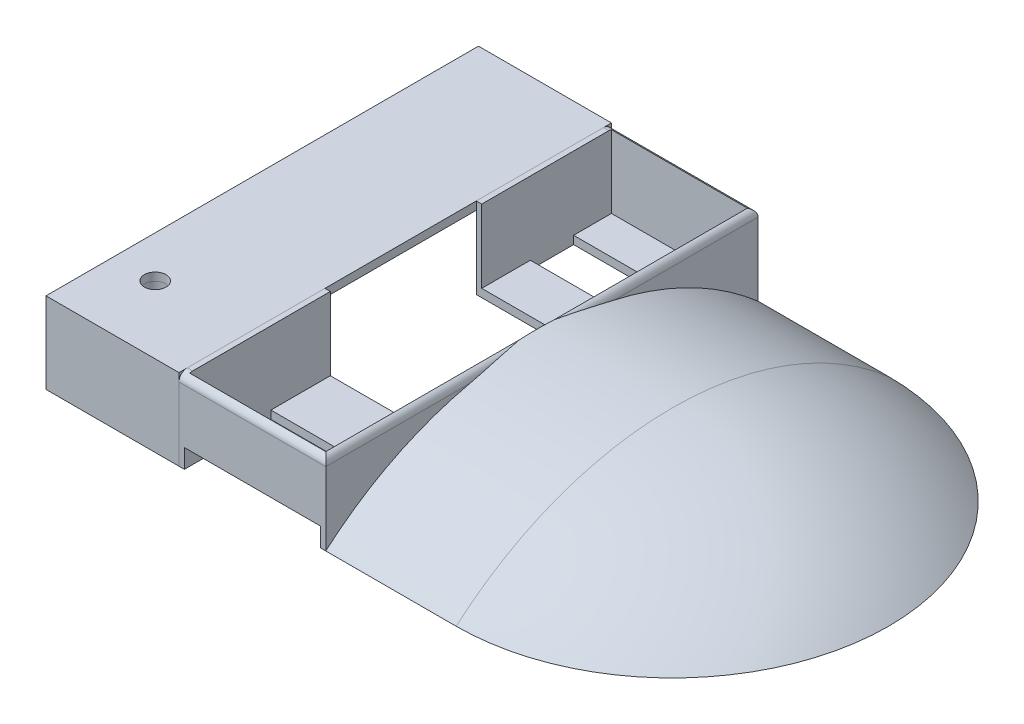
SolidWorks part; units mm, degrees
note: The reader was unsure of these and kept them because the rebuilt part matched: shared geometry of "Sketch11<3>", "Sketch47<2>".
ref_plane "Front Plane" through (0, 0, 0) normal (0, 0, 1) x (1, 0, 0)
ref_plane "Top Plane" through (0, 0, 0) normal (0, 1, 0) x (1, 0, 0)
ref_plane "Right Plane" through (0, 0, 0) normal (1, 0, 0) x (0, 0, -1)
sketch3d "3DSketch2"
  line L1 (0.225, 29.25, -28.4) -> (24.375, 23.2287, -28.4) construction
  dimension "D1" = 0
sketch3d "3DSketch4" plane through (0, 0, 0) normal (0, 0, 1) x (1, 0, 0)
  dimension "D1" = 50
sketch "Sketch1" plane through (0, 0, 0) normal (0, 1, 0) x (1, 0, 0)
  line L1 (-25.875, -40) -> (25.875, -40)
  line L2 (-25.875, -40) -> (-25.875, 40)
  line L3 (-25.875, 40) -> (25.875, 40)
  line L4 (25.875, -40) -> (25.875, 40)
  line L5 (-25.875, -40) -> (25.875, 40) construction
  line L6 (-25.875, 40) -> (25.875, -40) construction
  point P0 (0, 0)
  dimension "D1" = 80
  dimension "D2" = 51.75
extrude "Boss-Extrude1" add sketch "Sketch1" along normal blind 15
shell "Shell3" thickness 1.5
sketch "Sketch4" plane through (-25.875, 0, 0) normal (-1, 0, 0) x (0, 0, 1)
  line L0 (-34.38, 1.6) -> (-28.48, 1.6) construction
  line L1 (-34.38, 3.4) -> (-28.48, 3.4)
  line L2 (-34.38, -0.2) -> (-28.48, -0.2)
  line L3 (-40, 15) -> (-40, 0) construction
  arc A0 (-34.38, 3.4) -> (-34.38, -0.2) centre (-34.38, 1.6) ccw
  arc A1 (-28.48, -0.2) -> (-28.48, 3.4) centre (-28.48, 1.6) ccw
  point P2 (-31.43, 1.6)
  dimension "D1" = 8.57
  dimension "D2" = 5.9
  dimension "D3" = 3.6
extrude "Cut-Extrude2" cut sketch "Sketch4" against normal blind 1.5
sketch "Sketch6" plane through (-25.875, 0, 0) normal (-1, 0, 0) x (0, 0, 1)
  line L0 (-27.6554, 0) -> (40, 0) construction
  line L1 (-24.4, 7.3) -> (-10.75, 7.3)
  line L2 (-24.4, 7.3) -> (-24.4, 0)
  line L3 (-24.4, 0) -> (-10.75, 0)
  line L4 (-10.75, 7.3) -> (-10.75, 0)
  line L5 (-24.4, 7.3) -> (-10.75, 0) construction
  line L6 (-24.4, 0) -> (-10.75, 7.3) construction
  line L8 (-40, 15) -> (-40, 0) construction
  point P6 (-17.575, 3.65)
  dimension "D1" = 7.3
  dimension "D2" = 13.65
  dimension "D3" = 0
  dimension "D4" = 22.425
extrude "Cut-Extrude3" cut sketch "Sketch6" against normal blind 1.5
sketch "Sketch11" plane through (0, 15, 0) normal (0, 1, 0) x (1, 0, 0)
  line L0 (-25.875, -40) -> (25.875, -40) construction
  line L1 (-25.875, 40) -> (-25.875, -40) construction
  circle A0 centre (-18.175, -27.5) radius 2
  dimension "D1" = 7.7
  dimension "D2" = 12.5
  dimension "D3" = 4
extrude "Boss-Extrude10" add sketch "Sketch11" against normal blind 11
extrude "Cut-Extrude10" cut sketch "Sketch11<3>" against normal blind 1.5
sketch "Sketch11<3>" plane through (0, 15, 0) normal (0, 1, 0) x (1, 0, 0) same geometry as "Sketch11"
shell "Shell9" thickness 1
sketch "Sketch45" plane through (6.8792, 27.5909, 0) normal (-0.2419, -0.9703, 0) x (-0.9703, 0.2419, 0)
  line L5 (-111.6083, -40) -> (6.8579, -40)
  line L6 (-111.6083, -40) -> (-111.6083, 40)
  line L7 (-111.6083, 40) -> (6.8579, 40)
  line L8 (6.8579, -40) -> (6.8579, 40)
sketch "Sketch47" plane through (0, 0, 40) normal (0, 0, 1) x (1, 0, 0)
  line L1 (-1.275, 0) -> (25.875, 0)
  line L2 (-1.275, 0) -> (-1.275, 15)
  line L3 (-1.275, 15) -> (25.875, 15)
  line L4 (25.875, 0) -> (25.875, 15)
  line L5 (-25.875, 15) -> (-25.875, 0) construction
  line L6 (-19.875, 0) -> (25.875, 0) construction
  dimension "D1" = 27.15
  dimension "D2" = 24.6
  dimension "D3" = 0
extrude "Cut-Extrude15" cut sketch "Sketch47" against normal through all
extrude "Boss-Extrude12" add sketch "Sketch47<2>" against normal blind 80 separate body
sketch "Sketch47<2>" plane through (0, 0, 40) normal (0, 0, 1) x (1, 0, 0) same geometry as "Sketch47"
shell "Shell15" thickness 1
sketch "Sketch52" plane through (0, 0, 39) normal (0, 0, -1) x (-1, 0, 0)
  line L0 (0.275, 15) -> (0.275, 1.5) construction
  line L1 (-24.875, 0) -> (0.275, 0)
  line L2 (-24.875, 0) -> (-24.875, 3.5)
  line L3 (-24.875, 3.5) -> (0.275, 3.5)
  line L4 (0.275, 0) -> (0.275, 3.5)
  line L5 (0.275, 15) -> (0.275, 1.5) construction
  line L6 (0.275, 14.9142) -> (-24.875, 14.9142) construction
  dimension "D1" = 25.15
  dimension "D2" = 11.4142
extrude "Cut-Extrude21" cut sketch "Sketch52" against normal blind 1
sketch "Sketch54" plane through (-0.275, 0, 0) normal (1, 0, 0) x (0, 0, -1)
  line L0 (-39, 0) -> (-40, 0) construction
  line L5 (15, 15) -> (-13, 15)
  line L6 (15, 15) -> (15, 0)
  line L7 (15, 0) -> (-13, 0)
  line L8 (-13, 15) -> (-13, 0)
  line L9 (15, 15) -> (-13, 0) construction
  line L10 (15, 0) -> (-13, 15) construction
  line L12 (40, 15) -> (40, 0) construction
  line L13 (-40, 15) -> (-40, 0) construction
  point P0 (1, 7.5)
  dimension "D1" = 15
  dimension "D2" = 25
  dimension "D3" = 27
extrude "Cut-Extrude22" cut sketch "Sketch54" against normal blind 1
sketch "Sketch55" plane through (0, 1.5, 0) normal (0, 1, 0) x (1, 0, 0)
  line L1 (24.875, -39) -> (-0.275, -39)
  line L2 (24.875, -39) -> (24.875, -24)
  line L3 (24.875, -24) -> (-0.275, -24)
  line L4 (-0.275, -39) -> (-0.275, -24)
  line L6 (-1.275, -13) -> (24.875, -13)
  line L7 (-1.275, -13) -> (-1.275, 15)
  line L8 (-1.275, 15) -> (24.875, 15)
  line L9 (24.875, -13) -> (24.875, 15)
  line L12 (-0.275, 32) -> (24.875, 32)
  line L13 (-0.275, 32) -> (-0.275, 24)
  line L14 (-0.275, 24) -> (24.875, 24)
  line L15 (24.875, 32) -> (24.875, 24)
  line L16 (-1.275, 40) -> (25.875, 40) construction
  line L17 (25.875, 40) -> (25.875, -40) construction
  line L18 (25.875, -40) -> (-1.275, -40) construction
  line L19 (-25.875, -40) -> (-1.275, -40) construction
  line L20 (-1.275, 40) -> (-25.875, 40) construction
  dimension "D1" = 8
  dimension "D2" = 16
  dimension "D3" = 25
  dimension "D4" = 16
  dimension "D5" = 53
  dimension "D6" = 1
  dimension "D7" = 1
  dimension "D8" = 1
  dimension "D9" = 1
  dimension "D10" = 27.15
  dimension "D11" = 26.15
  dimension "D12" = 26.15
extrude "Cut-Extrude23" cut sketch "Sketch55" against normal blind 1.5
sketch "Sketch63" plane through (50, 0, 0) normal (1, 0, 0) x (0, 0, -1)
  line L1 (-40, 0) -> (40, 0)
  arc A0 (-40, 0) -> (40, 0) centre (0, -45.83) cw
  dimension "D1" = 60.8308
sketch "Sketch64" plane through (0, 0, -40) normal (0, 0, -1) x (-1, 0, 0)
  line L0 (-25.875, 0) -> (-50, 0)
sketch "Sketch65" plane through (0, 0, 40) normal (0, 0, 1) x (1, 0, 0)
  line L0 (25.875, 0) -> (50, 0)
extrude "Boss-Extrude13" add sketch "Sketch63" against normal blind 24.13 contours A0 L1
sketch "Sketch69" plane through (50, 0, 0) normal (1, 0, 0) x (0, 0, -1)
  line L1 (0, 15.0008) -> (0, 0)
  line L2 (0, 0) -> (-40, 0)
  arc A0 (40, 0) -> (-40, 0) centre (0, -45.83) ccw construction
  arc A1 (-40, 0) -> (0, 15.0008) centre (0, -45.83) cw
revolve "Revolve5" add sketch "Sketch69" angle 180 about L1
fillet "Fillet1" radius 1.5 3 edges at (12.3, 15, -40) (25.875, 15, -20.1581) (12.3, 15, 40)
